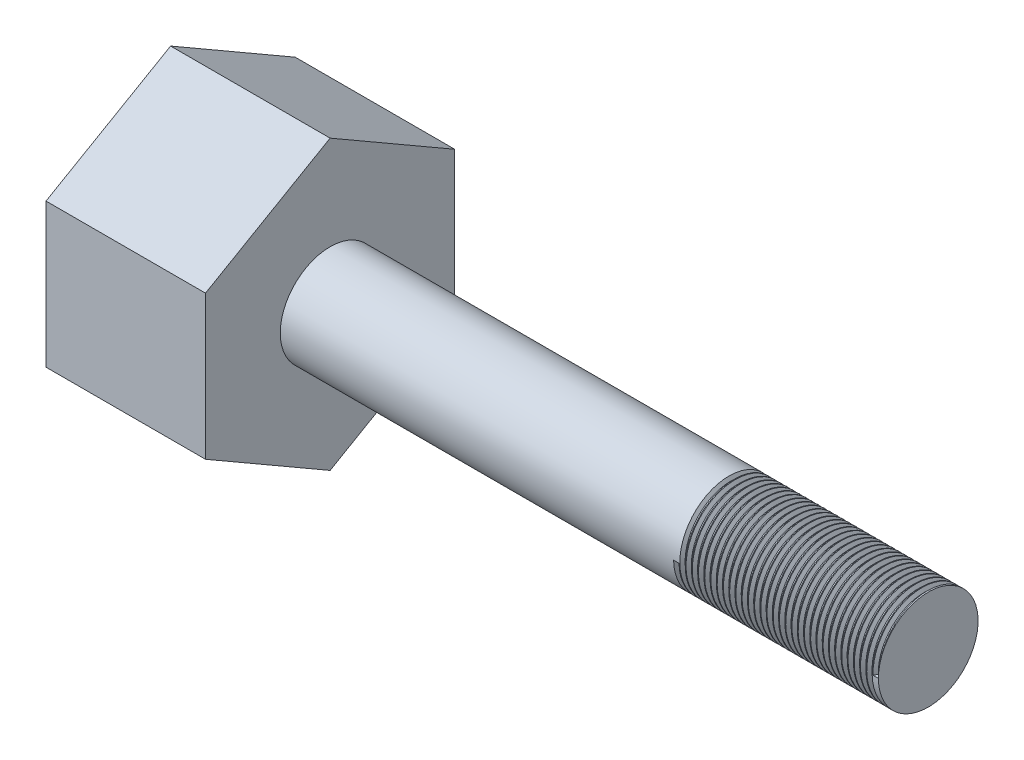
SolidWorks part; units mm, degrees
ref_plane "Front Plane" through (0, 0, 0) normal (1, 0, 0) x (0, 1, 0)
ref_plane "Top Plane" through (0, 0, 0) normal (0, 0, 1) x (0, 1, 0)
ref_plane "Right Plane" through (0, 0, 0) normal (0, 1, 0) x (-1, 0, 0)
sketch "Sketch1" plane through (0, 0, 0) normal (1, 0, 0) x (0, 1, 0)
  line L1 (28.8675, 0) -> (14.4338, 25)
  line L2 (14.4338, 25) -> (-14.4338, 25)
  line L3 (-14.4338, 25) -> (-28.8675, 0)
  line L4 (-28.8675, 0) -> (-14.4338, -25)
  line L5 (-14.4338, -25) -> (14.4338, -25)
  line L6 (14.4338, -25) -> (28.8675, 0)
  circle A0 centre (0, 0) radius 25 construction
  dimension "D1" = 50
extrude "Boss-Extrude4" add sketch "Sketch1" along normal blind 32
sketch "Sketch16" plane through (32, 0, 0) normal (1, 0, 0) x (0, 1, 0)
  circle A0 centre (0, 0) radius 10
  dimension "D1" = 20
extrude "Boss-Extrude5" add sketch "Sketch16" along normal blind 120
thread "Thread4" pitch 1.25 method cut profile "Thread Profile4" start angle 0, offset 0, length 40, pitch 1.25, diameter 20
ref_plane "Plane4" through (152, 0, 10) normal (0, -1, 0) x (0, 0, 1)
sketch "Thread Profile4" plane through (152, 0, 10) normal (0, -1, 0) x (0, 0, 1)
  line L0 (0, 0) -> (0, 1.25) construction
  line L11 (0, 0) -> (0, 1.0937)
  line L12 (0, 1.0937) -> (-0.6766, 0.7031)
  line L13 (-0.6766, 0.7031) -> (-0.6766, 0.3906)
  line L15 (-0.6766, 0.3906) -> (0, 0)
  line L17 (-0.6766, 0.5469) -> (0, 0.5469) construction
  point P2 (0, 0)
  dimension "Pitch" = 1.25
  dimension "Profile_Angle" = 60
  dimension "Profile_Land" = 0.3125
  dimension "Profile_Height" = 0.6766
